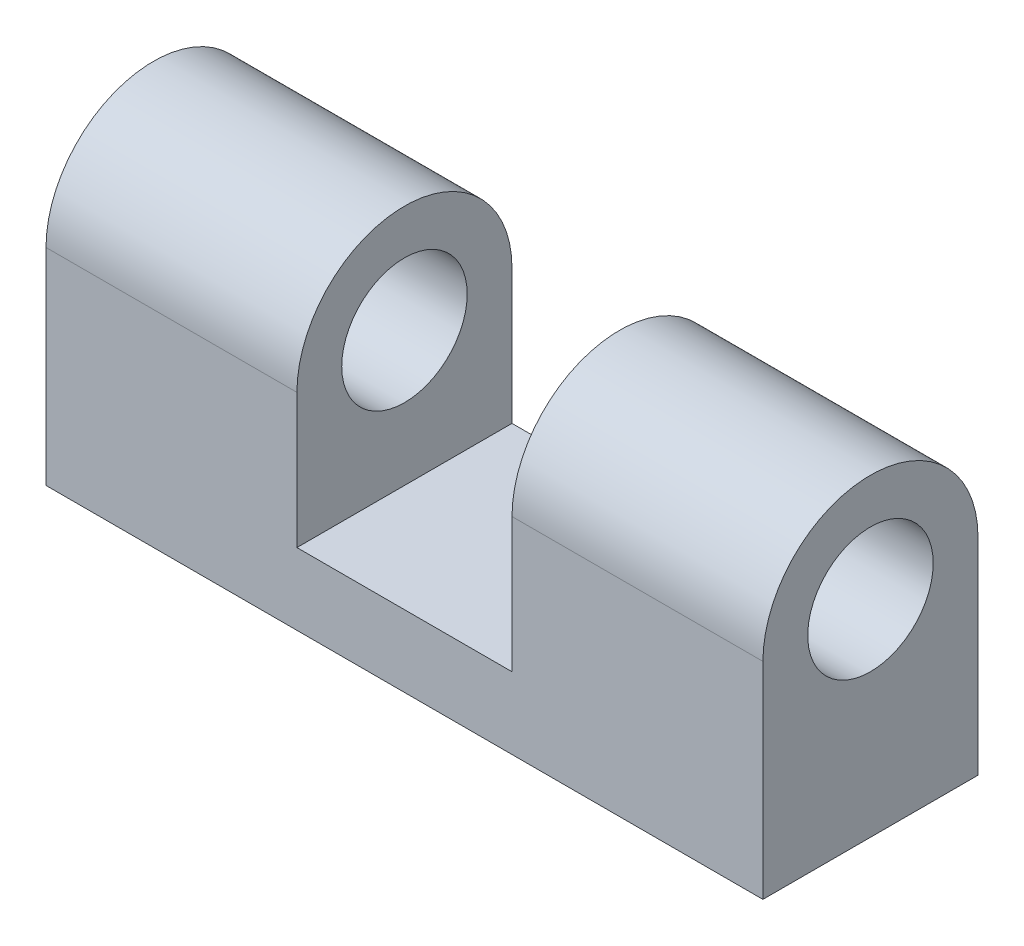
SolidWorks part; units mm, degrees
ref_plane "Plano frontal" through (0, 0, 0) normal (0, 0, 1) x (1, 0, 0)
ref_plane "Plano superior" through (0, 0, 0) normal (0, 1, 0) x (1, 0, 0)
ref_plane "Plano direito" through (0, 0, 0) normal (1, 0, 0) x (0, 0, -1)
sketch "Esboço3" plane through (0, 0, 0) normal (0, 1, 0) x (1, 0, 0)
  circle A1 centre (0, 0) radius 15
  dimension "D2" = 30
extrude "Ressalto-extrusão2" add sketch "Esboço3" along normal blind 20
sketch "Esboço5" plane through (0, 0, 0) normal (1, 0, 0) x (0, 0, -1)
  line L0 (0, 20) -> (0, 28.75) construction
  line L1 (15, 20) -> (-15, 20) construction
  circle A0 centre (0, 28.75) radius 15
  circle A1 centre (0, 28.75) radius 8.75
  dimension "D2" = 17.5
  dimension "D3" = 30
extrude "Ressalto-extrusão3" add sketch "Esboço5" along normal blind 50 and the other way blind 50 separate body
sketch "Esboço6" plane through (0, 0, 0) normal (0, 1, 0) x (1, 0, 0)
  line L0 (50, 15) -> (-50, 15) construction
  line L1 (-15, 15) -> (15, 15)
  line L2 (-15, 15) -> (-15, -15)
  line L3 (-15, -15) -> (15, -15)
  line L4 (15, 15) -> (15, -15)
  line L5 (-15, 15) -> (15, -15) construction
  line L6 (-15, -15) -> (15, 15) construction
  point P0 (0, 0)
  dimension "D2" = 30
extrude "Corte-extrusão2" cut sketch "Esboço6" along normal through all from surface starting at face at (0, 20, 15)
sketch "Esboço7" plane through (0, 0, 0) normal (0, -1, 0) x (1, 0, 0)
  line L0 (50, -15) -> (50, 15) construction
  line L1 (-50, 15) -> (50, 15)
  line L2 (-50, 15) -> (-50, -15)
  line L3 (-50, -15) -> (50, -15)
  line L4 (50, 15) -> (50, -15)
extrude "Ressalto-extrusão4" add sketch "Esboço7" against normal up to surface (28.75 mm away) up to face at (0, 31.875, 0)
sketch "Esboço8" plane through (0, 20, 0) normal (0, 1, 0) x (1, 0, 0)
  line L1 (-15, 15) -> (15, 15)
  line L2 (-15, 15) -> (-15, -15)
  line L3 (-15, -15) -> (15, -15)
  line L4 (15, 15) -> (15, -15)
extrude "Corte-extrusão3" cut sketch "Esboço8" along normal through all and the other way blind 10
